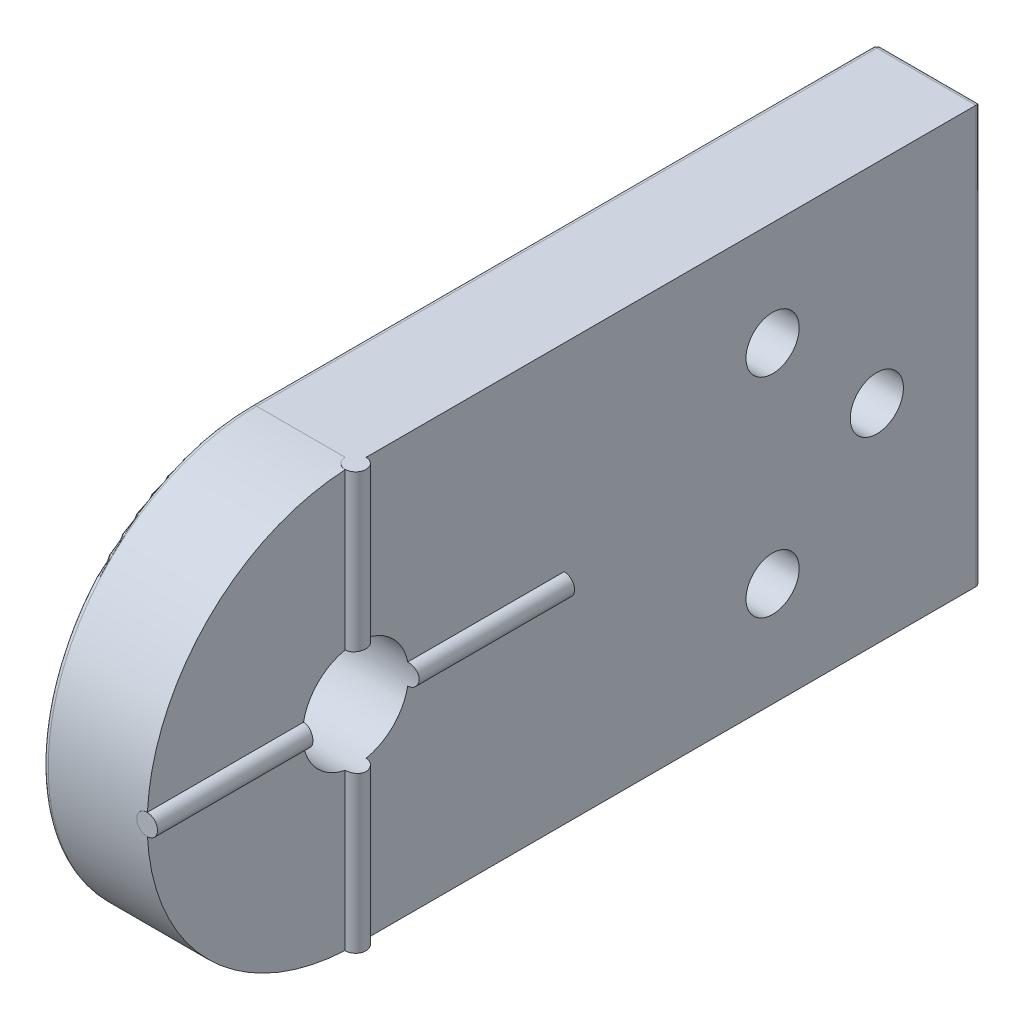
SolidWorks part; units mm, degrees
ref_plane "Front Plane" through (0, 0, 0) normal (0, 0, 1) x (1, 0, 0)
ref_plane "Top Plane" through (0, 0, 0) normal (0, 1, 0) x (1, 0, 0)
ref_plane "Right Plane" through (0, 0, 0) normal (1, 0, 0) x (0, 0, -1)
sketch "Sketch1" plane through (0, 0, 0) normal (1, 0, 0) x (0, 0, -1)
  line L1 (0, 20) -> (60, 20)
  line L3 (0, -20) -> (60, -20)
  line L4 (60, 20) -> (60, -20)
  arc A0 (0, 20) -> (0, -20) centre (0, 0) ccw
  dimension "D1" = 40
  dimension "D2" = 60
  dimension "D3" = 60
extrude "Boss-Extrude1" add sketch "Sketch1" along normal blind 10
sketch "Sketch3" plane through (10, 0, 0) normal (1, 0, 0) x (0, 0, -1)
  line L0 (0, 20) -> (0, -20)
sketch "Sketch4" plane through (10, 0, 0) normal (1, 0, 0) x (0, 0, -1)
  line L0 (-20, 0) -> (20, 0)
  arc A0 (0, 20) -> (0, -20) centre (0, 0) ccw construction
  dimension "D1" = 40
sketch "Sketch6" plane through (0, 0, 0) normal (-1, 0, 0) x (0, 0, 1)
  line L0 (-60, -20) -> (-60, 20) construction
  line L1 (-60, 20) -> (0, 20) construction
  line L2 (0, -20) -> (-60, -20) construction
  circle A0 centre (-40, 10) radius 2.55
  circle A1 centre (-50, 0) radius 2.55
  circle A2 centre (-40, -10) radius 2.55
  point P8 (-60, 0)
  dimension "D1" = 5.1
  dimension "D2" = 5.1
  dimension "D3" = 5.1
  dimension "D4" = 10
  dimension "D5" = 20
  dimension "D6" = 20
  dimension "D7" = 10
  dimension "D8" = 10
  dimension "D9" = 20
revolve "Revolve-Thin1" add sketch "Sketch3" angle 360 about L0 wall 1
revolve "Revolve-Thin2" add sketch "Sketch4" angle 360 about L0 wall 1
sketch "Sketch7" plane through (0, 0, 0) normal (-1, 0, 0) x (0, 0, 1)
  circle A0 centre (0, 0) radius 5.1
  dimension "D1" = 10.2
extrude "Cut-Extrude3" cut sketch "Sketch7" against normal through all
fillet "Fillet3" radius 0.5 5 edges at (0, -20, -30) (0, 0, -60) (0, 20, -30) (0, 0, 20) (0, 0, 5.1)
fillet "Fillet4" radius 0.5 5 edges at (0.1464, 19.8536, -59.8536) (0.1464, -19.8536, -59.8536) (5.25, 20, -60) (5.25, -20, -60) (10, 0, -60)
extrude "Cut-Extrude4" cut sketch "Sketch6" against normal through all
